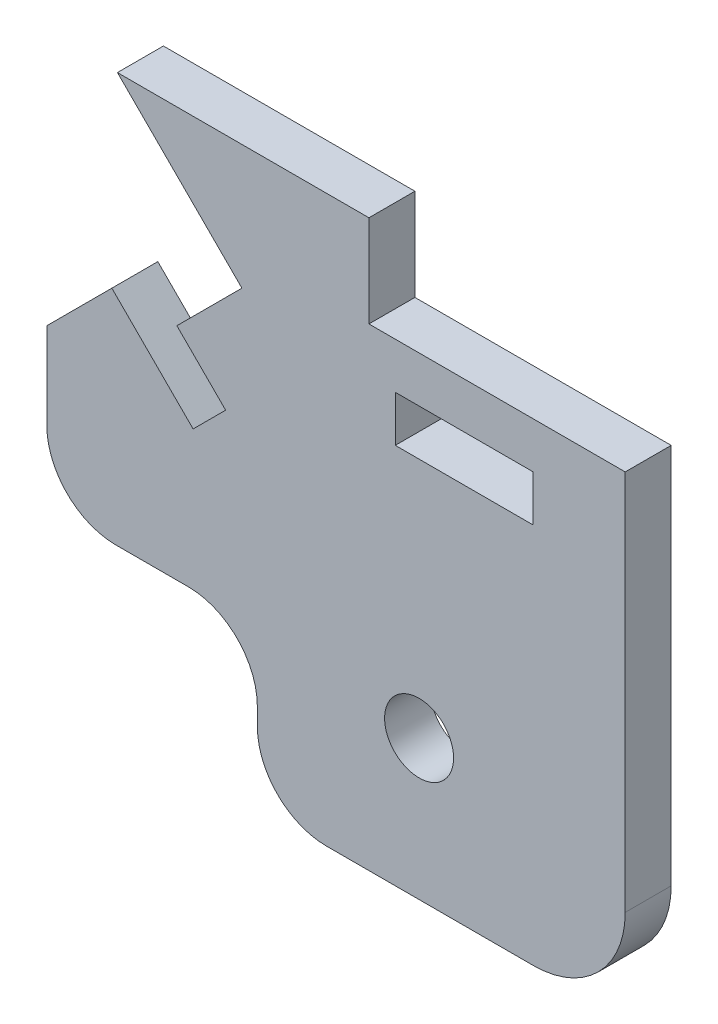
SolidWorks part; units mm, degrees
material "Acrylic (Medium-high impact)"
ref_plane "Front Plane" through (0, 0, 0) normal (0, 0, 1) x (1, 0, 0)
ref_plane "Top Plane" through (0, 0, 0) normal (0, 1, 0) x (1, 0, 0)
ref_plane "Right Plane" through (0, 0, 0) normal (1, 0, 0) x (0, 0, -1)
sketch "Model" plane through (0, 0, 0) normal (0, 0, 1) x (1, 0, 0)
  line L223 (6.364, 1.1716) -> (2.8284, 4.7071)
  line L224 (14.0104, 8.9497) -> (25.1569, 8.9497)
  line L225 (6.1569, -4.8787) -> (5.8284, -4.8787)
  line L226 (21.1569, -11.6414) -> (12.1569, -11.6414)
  line L227 (2.8284, 4.7071) -> (0, 1.8787)
  line L228 (3, -4.8787) -> (5.8284, -4.8787)
  line L229 (7.7782, 2.5858) -> (5.6569, 4.7071)
  line L230 (8.4853, 7.5355) -> (7.0711, 8.9497)
  line L231 (0, -1.8787) -> (0, 1.8787)
  line L232 (9.1569, -8.6414) -> (9.1569, -7.8787)
  line L233 (25.1569, 8.9497) -> (25.1569, -7.6414)
  line L234 (7.0711, 12.9497) -> (14.0104, 12.9497)
  line L235 (21.1569, 4.9497) -> (21.1569, 6.9497)
  line L236 (21.1569, 4.9497) -> (15.1569, 4.9497)
  line L237 (15.1569, 4.9497) -> (15.1569, 6.9497)
  line L238 (15.1569, 6.9497) -> (21.1569, 6.9497)
  line L255 (5.6569, 4.7071) -> (8.4853, 7.5355)
  line L256 (7.0711, 8.9497) -> (7.0711, 12.9497)
  line L257 (6.364, 1.1716) -> (7.7782, 2.5858)
  line L364 (14.0104, 8.9497) -> (14.0104, 12.9497)
  circle A99 centre (16.1917, -5.5589) radius 1.5
  arc A100 (21.1569, -11.6414) -> (25.1569, -7.6414) centre (21.1569, -7.6414) ccw
  arc A101 (9.1569, -8.6414) -> (12.1569, -11.6414) centre (12.1569, -8.6414) ccw
  arc A102 (9.1569, -7.8787) -> (6.1569, -4.8787) centre (6.1569, -7.8787) ccw
  arc A103 (0, -1.8787) -> (3, -4.8787) centre (3, -1.8787) ccw
  dimension "D1" = 3
  dimension "D2" = 4
  dimension "D3" = 3
  dimension "D4" = 5.6569
  dimension "D5" = 5.8284
  dimension "D6" = 6.364
  dimension "D7" = 9.1569
  dimension "D8" = 14.0104
  dimension "D9" = 16.1917
  dimension "D10" = 25.1569
  dimension "D11" = 1.1716
  dimension "D12" = 4.9497
  dimension "D20" = 4.8787
  dimension "D21" = 5.5589
  dimension "D22" = 11.6414
extrude "Boss-Extrude1" add sketch "Model" along normal blind 2
sketch "Sketch7" plane through (0, 0, 2) normal (0, 0, 1) x (1, 0, 0)
  line L0 (3.0711, 12.9497) -> (7.0711, 8.9497)
  line L1 (7.0711, 12.9497) -> (3.0711, 12.9497)
surface "Surface-Fill1"
sketch "Sketch10" plane through (0, 0, 2) normal (0, 0, 1) x (1, 0, 0)
  line L3 (7.0711, 12.9497) -> (3.0711, 12.9497)
  line L4 (7.0711, 8.9497) -> (7.0711, 12.9497)
  line L5 (3.0711, 12.9497) -> (7.0711, 8.9497)
  line L6 (7.0711, 12.9497) -> (3.0711, 12.9497)
  line L7 (7.0711, 8.9497) -> (7.0711, 12.9497)
  line L8 (3.0711, 12.9497) -> (7.0711, 8.9497)
  dimension "D1" = 0
extrude "Boss-Extrude2" add sketch "Sketch10" against normal blind 2
